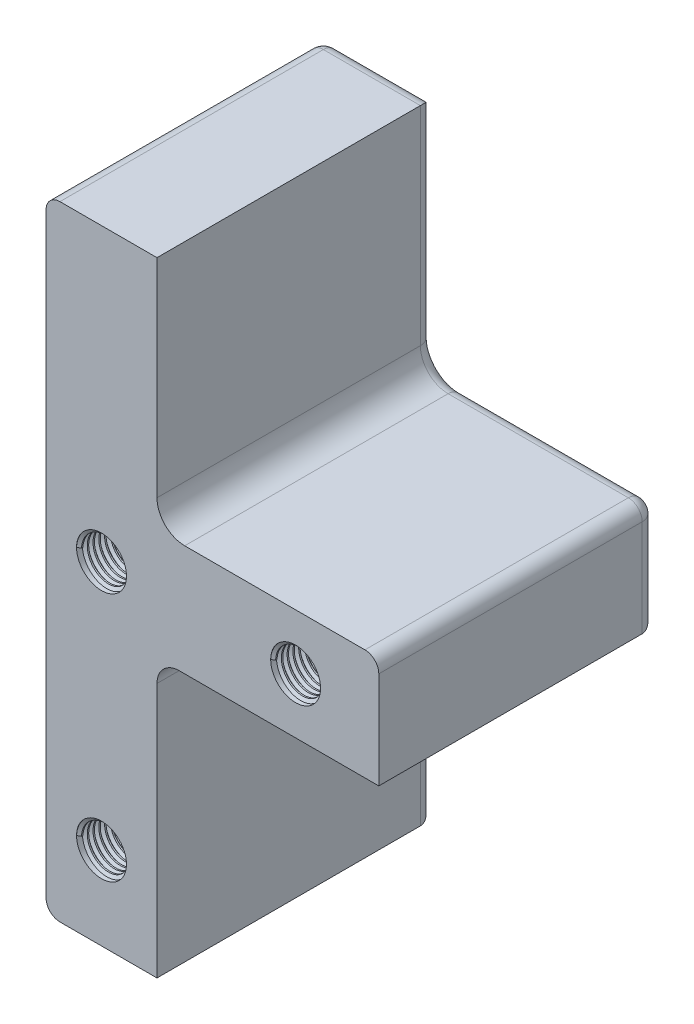
SolidWorks part; units mm, degrees
ref_plane "Front Plane" through (0, 0, 0) normal (0, 0, 1) x (1, 0, 0)
ref_plane "Top Plane" through (0, 0, 0) normal (0, 1, 0) x (1, 0, 0)
ref_plane "Right Plane" through (0, 0, 0) normal (1, 0, 0) x (0, 0, -1)
sketch "Sketch1" plane through (0, 0, 0) normal (0, 0, 1) x (1, 0, 0)
  line L0 (0, 0) -> (0, 35.56)
  line L2 (30.48, 35.56) -> (30.48, 25.4)
  line L3 (30.48, 25.4) -> (12.192, 25.4)
  line L4 (10.16, 23.368) -> (10.16, 0)
  line L5 (10.16, 0) -> (0, 0)
  line L6 (5.08, 0) -> (5.08, 7.62) construction
  line L7 (0, 35.56) -> (0, 57.15)
  line L8 (0, 57.15) -> (10.16, 57.15)
  line L9 (10.16, 57.15) -> (10.16, 38.1)
  line L10 (12.7, 35.56) -> (30.48, 35.56)
  circle A0 centre (5.08, 30.48) radius 2.286
  circle A1 centre (5.08, 7.62) radius 2.286
  circle A2 centre (22.86, 30.48) radius 2.286
  arc A3 (12.192, 25.4) -> (10.16, 23.368) centre (12.192, 23.368) ccw
  arc A4 (10.16, 38.1) -> (12.7, 35.56) centre (12.7, 38.1) ccw
  point P20 (10.16, 25.4)
  dimension "D1" = 4.572
  dimension "D2" = 5.08
  dimension "D8" = 2.032
  dimension "D11" = 2.54
  dimension "D9" = 4.572
  dimension "D3" = 7.62
  dimension "D4" = 30.48
  dimension "D5" = 22.86
  dimension "D6" = 10.16
  dimension "D7" = 17.78
  dimension "D10" = 57.15
  dimension "D12" = 23.368
extrude "Boss-Extrude1" add sketch "Sketch1" along normal blind 25.4
thread "Thread1" pitch 0.5292 method extrude profile "Thread Profile1" start angle 0, offset 0, length 14.732, pitch 0.5292, diameter 4.572
ref_plane "Plane1" through (2.794, 7.62, 25.4) normal (0, -1, 0) x (-1, 0, 0)
sketch "Thread Profile1" plane through (2.794, 7.62, 25.4) normal (0, -1, 0) x (-1, 0, 0)
  line L0 (0, 0) -> (0, 0.5292) construction
  line L11 (0, 0) -> (0, 0.463)
  line L12 (0, 0.463) -> (-0.2864, 0.2977)
  line L13 (-0.2864, 0.2977) -> (-0.2864, 0.1654)
  line L15 (-0.2864, 0.1654) -> (0, 0)
  line L17 (-0.2864, 0.2315) -> (0, 0.2315) construction
  point P2 (0, 0)
  dimension "Pitch" = 0.5292
  dimension "Profile_Angle" = 60
  dimension "Profile_Land" = 0.1323
  dimension "Profile_Height" = 0.2864
thread "Thread2" pitch 0.5292 method extrude profile "Thread Profile2" start angle 0, offset 0, length 14.732, pitch 0.5292, diameter 4.572
ref_plane "Plane2" through (2.794, 30.48, 25.4) normal (0, -1, 0) x (-1, 0, 0)
sketch "Thread Profile2" plane through (2.794, 30.48, 25.4) normal (0, -1, 0) x (-1, 0, 0)
  line L0 (0, 0) -> (0, 0.5292) construction
  line L11 (0, 0) -> (0, 0.463)
  line L12 (0, 0.463) -> (-0.2864, 0.2977)
  line L13 (-0.2864, 0.2977) -> (-0.2864, 0.1654)
  line L15 (-0.2864, 0.1654) -> (0, 0)
  line L17 (-0.2864, 0.2315) -> (0, 0.2315) construction
  point P2 (0, 0)
  dimension "Pitch" = 0.5292
  dimension "Profile_Angle" = 60
  dimension "Profile_Land" = 0.1323
  dimension "Profile_Height" = 0.2864
thread "Thread3" pitch 0.5292 method extrude profile "Thread Profile3" start angle 0, offset 0, length 14.732, pitch 0.5292, diameter 4.572
ref_plane "Plane3" through (20.574, 30.48, 25.4) normal (0, -1, 0) x (-1, 0, 0)
sketch "Thread Profile3" plane through (20.574, 30.48, 25.4) normal (0, -1, 0) x (-1, 0, 0)
  line L0 (0, 0) -> (0, 0.5292) construction
  line L11 (0, 0) -> (0, 0.463)
  line L12 (0, 0.463) -> (-0.2864, 0.2977)
  line L13 (-0.2864, 0.2977) -> (-0.2864, 0.1654)
  line L15 (-0.2864, 0.1654) -> (0, 0)
  line L17 (-0.2864, 0.2315) -> (0, 0.2315) construction
  point P2 (0, 0)
  dimension "Pitch" = 0.5292
  dimension "Profile_Angle" = 60
  dimension "Profile_Land" = 0.1323
  dimension "Profile_Height" = 0.2864
fillet "Fillet1" radius 1.27 13 edges at (0, 0, 12.7) (0, 57.15, 12.7) (0, 28.575, 0) (5.08, 0, 0) (10.16, 47.625, 0) (10.9039, 36.3039, 0) (21.59, 35.56, 0) (21.336, 25.4, 0) (10.7552, 24.8048, 0) (10.16, 11.684, 0) (5.08, 57.15, 0) (30.48, 35.56, 12.7) (30.48, 30.48, 0)
